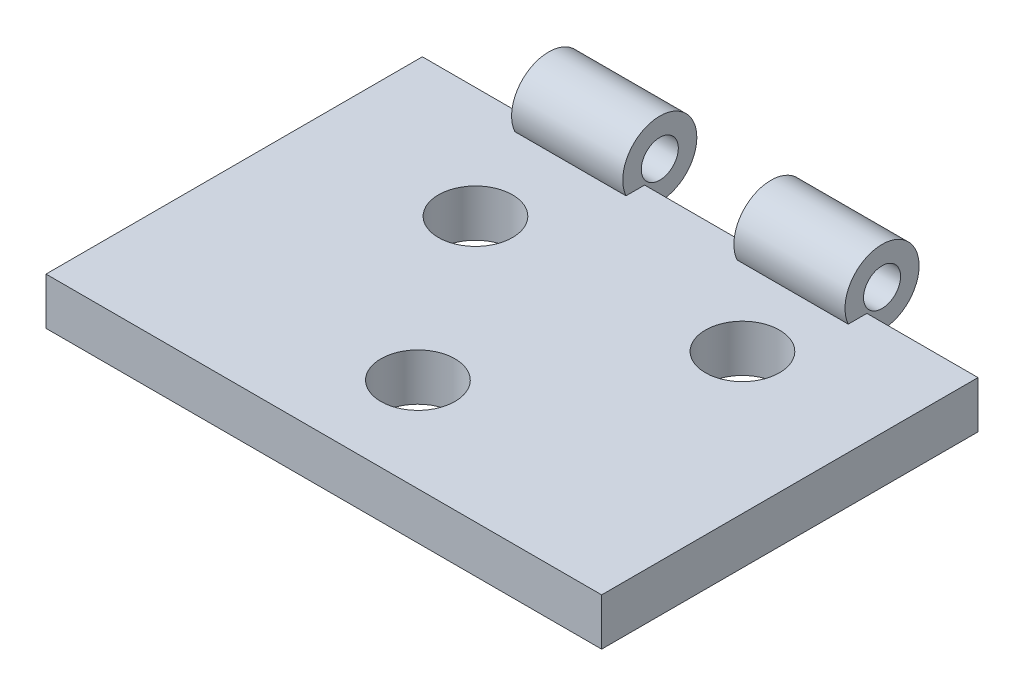
SolidWorks part; units mm, degrees
ref_plane "Front Plane" through (0, 0, 0) normal (0, 0, 1) x (1, 0, 0)
ref_plane "Top Plane" through (0, 0, 0) normal (0, 1, 0) x (1, 0, 0)
ref_plane "Right Plane" through (0, 0, 0) normal (1, 0, 0) x (0, 0, -1)
sketch "Sketch1" plane through (0, 0, 0) normal (0, 1, 0) x (1, 0, 0)
  line L0 (0, 0) -> (-37.5, 0)
  line L1 (-37.5, -25.4) -> (37.5, -25.4)
  line L2 (-37.5, -25.4) -> (-37.5, 25.4)
  line L3 (-37.5, 25.4) -> (37.5, 25.4)
  line L4 (37.5, -25.4) -> (37.5, 25.4)
  line L5 (-37.5, -25.4) -> (37.5, 25.4) construction
  line L6 (-37.5, 25.4) -> (37.5, -25.4) construction
  line L7 (0, 0) -> (37.5, 0)
  line L8 (37.5, 0) -> (18.75, 0)
  line L9 (-37.5, 0) -> (-18.75, 0)
  line L10 (0, 0) -> (0, -25.4)
  line L11 (0, -25.4) -> (0, -12.7)
  circle A0 centre (-15.2792, 10.3491) radius 5
  circle A1 centre (18.5438, 12.5604) radius 5
  circle A2 centre (0, -12.7) radius 5
  point P0 (0, 0)
  dimension "D3" = 10
  dimension "D4" = 10
  dimension "D5" = 10
  dimension "D1" = 75
  dimension "D2" = 50.8
extrude "Boss-Extrude1" add sketch "Sketch1" along normal blind 6.35 contours L0 L7 L4 L3 L2 A1 A0 | A2 L10 L0 L2 L1 L11 | A2 L11 L1 L4 L7 L10 region at (-19.465, 0, 12.7) region at (-0.1467, 0, -12.8119) region at (19.465, 0, 12.7)
sketch "Sketch2" plane through (-37.5, 0, 0) normal (-1, 0, 0) x (0, 0, 1)
  line L0 (-25.4, 6.35) -> (-32.2813, 13.2313)
  circle A0 centre (-27.4485, 8.3985) radius 5
  circle A1 centre (-27.4485, 8.3985) radius 2.5
  dimension "D1" = 10
  dimension "D2" = 2.5
extrude "Boss-Extrude2" add sketch "Sketch2" against normal blind 15 from offset 15 contours A0 offset against normal yes
pattern_linear "LPattern1" count 2 spacing 30 along (1, 0, 0) of "Boss-Extrude2"
extrude "Cut-Extrude2" cut sketch "Sketch2<4>" against normal through all contours A1
sketch "Sketch2<4>" plane through (-37.5, 0, 0) normal (-1, 0, 0) x (0, 0, 1) same geometry as "Sketch2"
sketch "Sketch3" plane through (0, 0, 0) normal (0, 1, 0) x (1, 0, 0)
  line L1 (-37.5, 25.4) -> (37.5, 25.4)
  line L2 (-37.5, 25.4) -> (-37.5, -25.4)
  line L3 (-37.5, -25.4) -> (37.5, -25.4)
  line L4 (37.5, 25.4) -> (37.5, -25.4)
  line L5 (-37.5, 25.4) -> (37.5, -25.4) construction
  line L6 (-37.5, -25.4) -> (37.5, 25.4) construction
  point P0 (0, 0)
